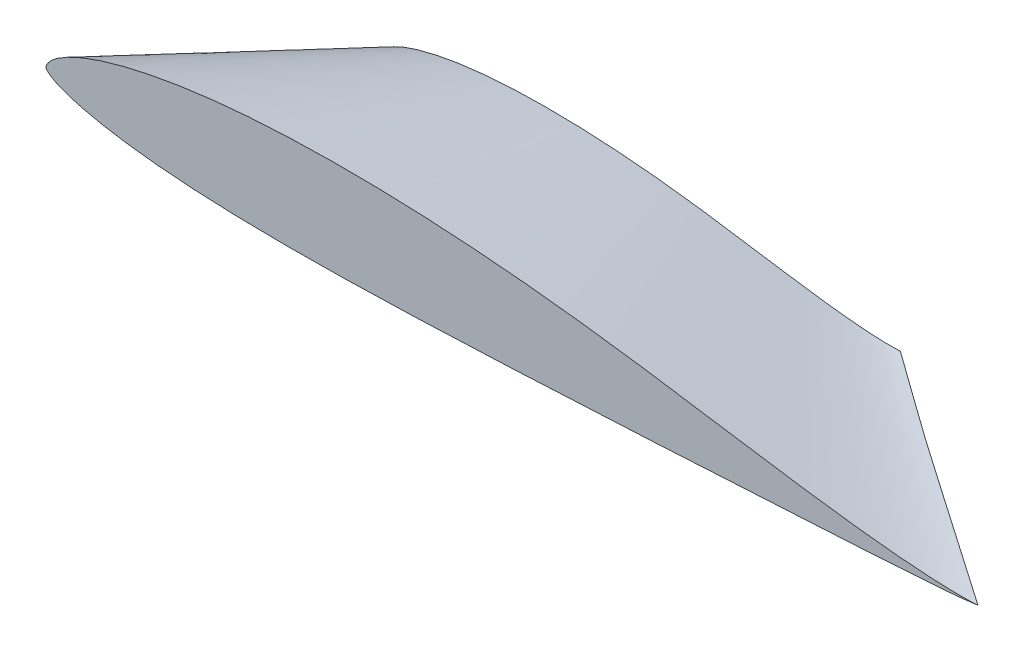
SolidWorks part; units mm, degrees
ref_plane "Front Plane" through (0, 0, 0) normal (0, 0, 1) x (1, 0, 0)
ref_plane "Top Plane" through (0, 0, 0) normal (0, 1, 0) x (1, 0, 0)
ref_plane "Right Plane" through (0, 0, 0) normal (1, 0, 0) x (0, 0, -1)
curve "Curve1"
  spline degree 3 poles (178.8235, -0.1536, 0) (180.3162, 0.0326, 0) (178.6769, -0.0979, 0) (177.3268, -0.1109, 0) (173.9976, -0.1057, 0) (169.9397, 0.1046, 0) (164.6882, 0.4858, 0) (158.5901, 1.1026, 0) (151.6988, 1.9482, 0) (144.1808, 2.9934, 0) (136.1635, 4.1927, 0) (127.7797, 5.4908, 0) (119.1442, 6.8173, 0) (110.3463, 8.0754, 0) (101.4587, 9.2, 0) (92.5465, 10.1562, 0) (83.6758, 10.9156, 0) (74.9166, 11.4682, 0) (66.342, 11.806, 0) (58.028, 11.9274, 0) (50.0487, 11.8319, 0) (42.4741, 11.515, 0) (35.367, 10.9819, 0) (28.7822, 10.24, 0) (22.7701, 9.3088, 0) (17.3773, 8.2269, 0) (12.6499, 7.0268, 0) (8.6305, 5.74, 0) (5.3502, 4.4039, 0) (2.8359, 3.0632, 0) (1.2518, 1.9009, 0) (0.4818, 1.0554, 0) (0.1891, 0.6046, 0) (0.0579, 0.3158, 0) (-0.0016, 0.0856, 0) (-0.0042, -0.0985, 0) (0.0738, -0.2696, 0) (0.2282, -0.4702, 0) (0.4808, -0.7088, 0) (0.9335, -1.0446, 0) (2.0075, -1.6855, 0) (4.0408, -2.5002, 0) (7.1529, -3.4084, 0) (11.097, -4.2605, 0) (15.8307, -5.0186, 0) (21.3187, -5.6503, 0) (27.5191, -6.1332, 0) (34.3853, -6.4628, 0) (41.8623, -6.6344, 0) (49.8874, -6.6565, 0) (58.3886, -6.5391, 0) (67.2847, -6.306, 0) (76.4836, -5.9763, 0) (85.8843, -5.5795, 0) (95.3777, -5.1338, 0) (104.8501, -4.6614, 0) (114.1865, -4.1746, 0) (123.2728, -3.6881, 0) (131.998, -3.2085, 0) (140.2557, -2.7461, 0) (147.9458, -2.3044, 0) (154.9716, -1.8945, 0) (161.2526, -1.5152, 0) (166.6878, -1.1747, 0) (171.2749, -0.8603, 0) (174.7811, -0.5984, 0) (177.6251, -0.3216, 0) (178.8235, -0.1536, 0) (180.3162, 0.0326, 0) (178.6769, -0.0979, 0) knots -0.013312 -0.00609 -0.00158 0 0.001669 0.006747 0.015187 0.026742 0.041155 0.058129 0.077283 0.098227 0.12058 0.143966 0.168018 0.192451 0.217075 0.24171 0.266182 0.29031 0.313903 0.336767 0.358704 0.37954 0.399122 0.417322 0.434037 0.449154 0.462553 0.474139 0.483848 0.491647 0.497539 0.499898 0.501005 0.501951 0.502492 0.502956 0.503431 0.504004 0.505035 0.506276 0.508636 0.515301 0.524213 0.535296 0.548467 0.563638 0.580726 0.599619 0.62018 0.642246 0.665633 0.690118 0.715452 0.741354 0.76752 0.793634 0.819375 0.844429 0.868488 0.891259 0.912467 0.93185 0.949165 0.964196 0.976755 0.986688 0.99391 0.99842 1 1.001669 1.006747 1.015187 periodic
ref_plane "Plane1" through (0, 0, -35) normal (0, 0, 1) x (1, 0, 0)
sketch "Sketch2" plane through (0, 0, 0) normal (0, 0, 1) x (1, 0, 0)
  line L0 (180, 0) -> (0, 0) construction
  spline S0 degree 3 poles (178.8235, -0.1536) (180.3162, 0.0326) (178.6769, -0.0979) (177.3268, -0.1109) (173.9976, -0.1057) (169.9397, 0.1046) (164.6882, 0.4858) (158.5901, 1.1026) (151.6988, 1.9482) (144.1808, 2.9934) (136.1635, 4.1927) (127.7797, 5.4908) (119.1442, 6.8173) (110.3463, 8.0754) (101.4587, 9.2) (92.5465, 10.1562) (83.6758, 10.9156) (74.9166, 11.4682) (66.342, 11.806) (58.028, 11.9274) (50.0487, 11.8319) (42.4741, 11.515) (35.367, 10.9819) (28.7822, 10.24) (22.7701, 9.3088) (17.3773, 8.2269) (12.6499, 7.0268) (8.6305, 5.74) (5.3502, 4.4039) (2.8359, 3.0632) (1.2518, 1.9009) (0.4818, 1.0554) (0.1891, 0.6046) (0.0579, 0.3158) (-0.0016, 0.0856) (-0.0042, -0.0985) (0.0738, -0.2696) (0.2282, -0.4702) (0.4808, -0.7088) (0.9335, -1.0446) (2.0075, -1.6855) (4.0408, -2.5002) (7.1529, -3.4084) (11.097, -4.2605) (15.8307, -5.0186) (21.3187, -5.6503) (27.5191, -6.1332) (34.3853, -6.4628) (41.8623, -6.6344) (49.8874, -6.6565) (58.3886, -6.5391) (67.2847, -6.306) (76.4836, -5.9763) (85.8843, -5.5795) (95.3777, -5.1338) (104.8501, -4.6614) (114.1865, -4.1746) (123.2728, -3.6881) (131.998, -3.2085) (140.2557, -2.7461) (147.9458, -2.3044) (154.9716, -1.8945) (161.2526, -1.5152) (166.6878, -1.1747) (171.2749, -0.8603) (174.7811, -0.5984) (177.6251, -0.3216) (178.8235, -0.1536) (180.3162, 0.0326) (178.6769, -0.0979) knots -0.013312 -0.00609 -0.00158 0 0.001669 0.006747 0.015187 0.026742 0.041155 0.058129 0.077283 0.098227 0.12058 0.143966 0.168018 0.192451 0.217075 0.24171 0.266182 0.29031 0.313903 0.336767 0.358704 0.37954 0.399122 0.417322 0.434037 0.449154 0.462553 0.474139 0.483848 0.491647 0.497539 0.499898 0.501005 0.501951 0.502492 0.502956 0.503431 0.504004 0.505035 0.506276 0.508636 0.515301 0.524213 0.535296 0.548467 0.563638 0.580726 0.599619 0.62018 0.642246 0.665633 0.690118 0.715452 0.741354 0.76752 0.793634 0.819375 0.844429 0.868488 0.891259 0.912467 0.93185 0.949165 0.964196 0.976755 0.986688 0.99391 0.99842 1 1.001669 1.006747 1.015187 only from (180, 0) to (180, 0) construction
  spline S1 degree 3 poles (178.8235, -0.1536) (180.3162, 0.0326) (178.6769, -0.0979) (177.3268, -0.1109) (173.9976, -0.1057) (169.9397, 0.1046) (164.6882, 0.4858) (158.5901, 1.1026) (151.6988, 1.9482) (144.1808, 2.9934) (136.1635, 4.1927) (127.7797, 5.4908) (119.1442, 6.8173) (110.3463, 8.0754) (101.4587, 9.2) (92.5465, 10.1562) (83.6758, 10.9156) (74.9166, 11.4682) (66.342, 11.806) (58.028, 11.9274) (50.0487, 11.8319) (42.4741, 11.515) (35.367, 10.9819) (28.7822, 10.24) (22.7701, 9.3088) (17.3773, 8.2269) (12.6499, 7.0268) (8.6305, 5.74) (5.3502, 4.4039) (2.8359, 3.0632) (1.2518, 1.9009) (0.4818, 1.0554) (0.1891, 0.6046) (0.0579, 0.3158) (-0.0016, 0.0856) (-0.0042, -0.0985) (0.0738, -0.2696) (0.2282, -0.4702) (0.4808, -0.7088) (0.9335, -1.0446) (2.0075, -1.6855) (4.0408, -2.5002) (7.1529, -3.4084) (11.097, -4.2605) (15.8307, -5.0186) (21.3187, -5.6503) (27.5191, -6.1332) (34.3853, -6.4628) (41.8623, -6.6344) (49.8874, -6.6565) (58.3886, -6.5391) (67.2847, -6.306) (76.4836, -5.9763) (85.8843, -5.5795) (95.3777, -5.1338) (104.8501, -4.6614) (114.1865, -4.1746) (123.2728, -3.6881) (131.998, -3.2085) (140.2557, -2.7461) (147.9458, -2.3044) (154.9716, -1.8945) (161.2526, -1.5152) (166.6878, -1.1747) (171.2749, -0.8603) (174.7811, -0.5984) (177.6251, -0.3216) (178.8235, -0.1536) (180.3162, 0.0326) (178.6769, -0.0979) knots -0.013312 -0.00609 -0.00158 0 0.001669 0.006747 0.015187 0.026742 0.041155 0.058129 0.077283 0.098227 0.12058 0.143966 0.168018 0.192451 0.217075 0.24171 0.266182 0.29031 0.313903 0.336767 0.358704 0.37954 0.399122 0.417322 0.434037 0.449154 0.462553 0.474139 0.483848 0.491647 0.497539 0.499898 0.501005 0.501951 0.502492 0.502956 0.503431 0.504004 0.505035 0.506276 0.508636 0.515301 0.524213 0.535296 0.548467 0.563638 0.580726 0.599619 0.62018 0.642246 0.665633 0.690118 0.715452 0.741354 0.76752 0.793634 0.819375 0.844429 0.868488 0.891259 0.912467 0.93185 0.949165 0.964196 0.976755 0.986688 0.99391 0.99842 1 1.001669 1.006747 1.015187 only from (180, 0) to (180, 0)
  point P4 (0, 0)
curve "Curve2"
  spline degree 3 poles (129.3464, -0.0853, 0) (130.1757, 0.0181, 0) (129.2649, -0.0544, 0) (128.5149, -0.0616, 0) (126.6653, -0.0587, 0) (124.4109, 0.0581, 0) (121.4935, 0.2699, 0) (118.1056, 0.6125, 0) (114.2771, 1.0823, 0) (110.1004, 1.663, 0) (105.6464, 2.3293, 0) (100.9887, 3.0504, 0) (96.1912, 3.7874, 0) (91.3035, 4.4863, 0) (86.366, 5.1111, 0) (81.4147, 5.6423, 0) (76.4865, 6.0642, 0) (71.6203, 6.3712, 0) (66.8567, 6.5589, 0) (62.2378, 6.6263, 0) (57.8048, 6.5733, 0) (53.5967, 6.3972, 0) (49.6483, 6.1011, 0) (45.9901, 5.6889, 0) (42.65, 5.1716, 0) (39.654, 4.5705, 0) (37.0277, 3.9038, 0) (34.7947, 3.1889, 0) (32.9723, 2.4466, 0) (31.5755, 1.7018, 0) (30.6954, 1.0561, 0) (30.2677, 0.5864, 0) (30.1051, 0.3359, 0) (30.0322, 0.1755, 0) (29.9991, 0.0476, 0) (29.9977, -0.0547, 0) (30.041, -0.1498, 0) (30.1268, -0.2612, 0) (30.2671, -0.3938, 0) (30.5186, -0.5803, 0) (31.1153, -0.9364, 0) (32.2449, -1.389, 0) (33.9738, -1.8935, 0) (36.165, -2.3669, 0) (38.7949, -2.7881, 0) (41.8437, -3.1391, 0) (45.2884, -3.4073, 0) (49.1029, -3.5905, 0) (53.2568, -3.6858, 0) (57.7152, -3.6981, 0) (62.4381, -3.6328, 0) (67.3804, -3.5033, 0) (72.4909, -3.3202, 0) (77.7135, -3.0997, 0) (82.9876, -2.8521, 0) (88.2501, -2.5897, 0) (93.437, -2.3192, 0) (98.4849, -2.0489, 0) (103.3322, -1.7825, 0) (107.9198, -1.5256, 0) (112.1921, -1.2802, 0) (116.0954, -1.0525, 0) (119.5848, -0.8418, 0) (122.6043, -0.6526, 0) (125.1527, -0.4779, 0) (127.1006, -0.3325, 0) (128.6806, -0.1786, 0) (129.3464, -0.0853, 0) (130.1757, 0.0181, 0) (129.2649, -0.0544, 0) knots -0.013312 -0.00609 -0.00158 0 0.001669 0.006747 0.015187 0.026742 0.041155 0.058129 0.077283 0.098227 0.12058 0.143966 0.168018 0.192451 0.217075 0.24171 0.266182 0.29031 0.313903 0.336767 0.358704 0.37954 0.399122 0.417322 0.434037 0.449154 0.462553 0.474139 0.483848 0.491647 0.497539 0.499898 0.501005 0.501951 0.502492 0.502956 0.503431 0.504004 0.505035 0.506276 0.508636 0.515301 0.524213 0.535296 0.548467 0.563638 0.580726 0.599619 0.62018 0.642246 0.665633 0.690118 0.715452 0.741354 0.76752 0.793634 0.819375 0.844429 0.868488 0.891259 0.912467 0.93185 0.949165 0.964196 0.976755 0.986688 0.99391 0.99842 1 1.001669 1.006747 1.015187 periodic
sketch "Sketch3" plane through (0, 0, -35) normal (0, 0, 1) x (1, 0, 0)
  line L0 (130, 0) -> (29.9996, 0) construction
  spline S0 degree 3 poles (129.3464, -0.0853) (130.1757, 0.0181) (129.2649, -0.0544) (128.5149, -0.0616) (126.6653, -0.0587) (124.4109, 0.0581) (121.4935, 0.2699) (118.1056, 0.6125) (114.2771, 1.0823) (110.1004, 1.663) (105.6464, 2.3293) (100.9887, 3.0504) (96.1912, 3.7874) (91.3035, 4.4863) (86.366, 5.1111) (81.4147, 5.6423) (76.4865, 6.0642) (71.6203, 6.3712) (66.8567, 6.5589) (62.2378, 6.6263) (57.8048, 6.5733) (53.5967, 6.3972) (49.6483, 6.1011) (45.9901, 5.6889) (42.65, 5.1716) (39.654, 4.5705) (37.0277, 3.9038) (34.7947, 3.1889) (32.9723, 2.4466) (31.5755, 1.7018) (30.6954, 1.0561) (30.2677, 0.5864) (30.1051, 0.3359) (30.0322, 0.1755) (29.9991, 0.0476) (29.9977, -0.0547) (30.041, -0.1498) (30.1268, -0.2612) (30.2671, -0.3938) (30.5186, -0.5803) (31.1153, -0.9364) (32.2449, -1.389) (33.9738, -1.8935) (36.165, -2.3669) (38.7949, -2.7881) (41.8437, -3.1391) (45.2884, -3.4073) (49.1029, -3.5905) (53.2568, -3.6858) (57.7152, -3.6981) (62.4381, -3.6328) (67.3804, -3.5033) (72.4909, -3.3202) (77.7135, -3.0997) (82.9876, -2.8521) (88.2501, -2.5897) (93.437, -2.3192) (98.4849, -2.0489) (103.3322, -1.7825) (107.9198, -1.5256) (112.1921, -1.2802) (116.0954, -1.0525) (119.5848, -0.8418) (122.6043, -0.6526) (125.1527, -0.4779) (127.1006, -0.3325) (128.6806, -0.1786) (129.3464, -0.0853) (130.1757, 0.0181) (129.2649, -0.0544) knots -0.013312 -0.00609 -0.00158 0 0.001669 0.006747 0.015187 0.026742 0.041155 0.058129 0.077283 0.098227 0.12058 0.143966 0.168018 0.192451 0.217075 0.24171 0.266182 0.29031 0.313903 0.336767 0.358704 0.37954 0.399122 0.417322 0.434037 0.449154 0.462553 0.474139 0.483848 0.491647 0.497539 0.499898 0.501005 0.501951 0.502492 0.502956 0.503431 0.504004 0.505035 0.506276 0.508636 0.515301 0.524213 0.535296 0.548467 0.563638 0.580726 0.599619 0.62018 0.642246 0.665633 0.690118 0.715452 0.741354 0.76752 0.793634 0.819375 0.844429 0.868488 0.891259 0.912467 0.93185 0.949165 0.964196 0.976755 0.986688 0.99391 0.99842 1 1.001669 1.006747 1.015187 only from (130, 0) to (130, 0) construction
  spline S1 degree 3 poles (129.3464, -0.0853) (130.1757, 0.0181) (129.2649, -0.0544) (128.5149, -0.0616) (126.6653, -0.0587) (124.4109, 0.0581) (121.4935, 0.2699) (118.1056, 0.6125) (114.2771, 1.0823) (110.1004, 1.663) (105.6464, 2.3293) (100.9887, 3.0504) (96.1912, 3.7874) (91.3035, 4.4863) (86.366, 5.1111) (81.4147, 5.6423) (76.4865, 6.0642) (71.6203, 6.3712) (66.8567, 6.5589) (62.2378, 6.6263) (57.8048, 6.5733) (53.5967, 6.3972) (49.6483, 6.1011) (45.9901, 5.6889) (42.65, 5.1716) (39.654, 4.5705) (37.0277, 3.9038) (34.7947, 3.1889) (32.9723, 2.4466) (31.5755, 1.7018) (30.6954, 1.0561) (30.2677, 0.5864) (30.1051, 0.3359) (30.0322, 0.1755) (29.9991, 0.0476) (29.9977, -0.0547) (30.041, -0.1498) (30.1268, -0.2612) (30.2671, -0.3938) (30.5186, -0.5803) (31.1153, -0.9364) (32.2449, -1.389) (33.9738, -1.8935) (36.165, -2.3669) (38.7949, -2.7881) (41.8437, -3.1391) (45.2884, -3.4073) (49.1029, -3.5905) (53.2568, -3.6858) (57.7152, -3.6981) (62.4381, -3.6328) (67.3804, -3.5033) (72.4909, -3.3202) (77.7135, -3.0997) (82.9876, -2.8521) (88.2501, -2.5897) (93.437, -2.3192) (98.4849, -2.0489) (103.3322, -1.7825) (107.9198, -1.5256) (112.1921, -1.2802) (116.0954, -1.0525) (119.5848, -0.8418) (122.6043, -0.6526) (125.1527, -0.4779) (127.1006, -0.3325) (128.6806, -0.1786) (129.3464, -0.0853) (130.1757, 0.0181) (129.2649, -0.0544) knots -0.013312 -0.00609 -0.00158 0 0.001669 0.006747 0.015187 0.026742 0.041155 0.058129 0.077283 0.098227 0.12058 0.143966 0.168018 0.192451 0.217075 0.24171 0.266182 0.29031 0.313903 0.336767 0.358704 0.37954 0.399122 0.417322 0.434037 0.449154 0.462553 0.474139 0.483848 0.491647 0.497539 0.499898 0.501005 0.501951 0.502492 0.502956 0.503431 0.504004 0.505035 0.506276 0.508636 0.515301 0.524213 0.535296 0.548467 0.563638 0.580726 0.599619 0.62018 0.642246 0.665633 0.690118 0.715452 0.741354 0.76752 0.793634 0.819375 0.844429 0.868488 0.891259 0.912467 0.93185 0.949165 0.964196 0.976755 0.986688 0.99391 0.99842 1 1.001669 1.006747 1.015187 only from (130, 0) to (130, 0)
loft "Loft1" add profiles "Sketch2", "Sketch3" connector at (55.3868, 11.8834, 0) connector at (61.3985, 6.6053, -35)
mirror "Mirror1" [suppressed] about plane through (0, 0, 0) normal (0, 0, 1)
ref_axis "Axis4" through (0, 0, -61.6271) along (0, 0, 1)
ref_axis "Axis1" through (180, 0, 0) along (-1, 0, 0)
ref_axis "Axis2" through (130, 0, -35) along (-1, 0, 0)
ref_point "Point1"
ref_axis "Axis3" through (-0.0007, 0, 0) along (0.6508, 0, -0.7593)
sketch "Sketch4" plane through (0, 0, 0) normal (0, 1, 0) x (1, 0, 0)
  line L0 (0, 0) -> (141.8779, 107.8393) construction
  line L1 (0, 0) -> (100, 360) construction
  line L3 (25.3509, 91.2632) -> (60.0348, 45.6316) construction
  line L4 (94.7187, 0) -> (60.0348, 45.6316) construction
  line L5 (180, 0) -> (0, 0) construction
  dimension "D1" = 360
  dimension "D2" = 100
ref_plane "Plane2" through (0, 0, 0) normal (0.6051, 0, 0.7961) x (0.7961, 0, -0.6051)
sketch "Sketch5" plane through (0, 0, 0) normal (0.6051, 0, 0.7961) x (0.7961, 0, -0.6051)
  line L0 (42.0724, -26.6467) -> (53.5834, 38.635) construction
  line L1 (42.0724, -26.6467) -> (42.0724, 24.9899) construction
  dimension "D1" = 10
ref_axis "Axis5" through (33.623, -25.7352, -25.5564) along (0.1382, 0.9848, -0.1051)
ref_point "Point2"
